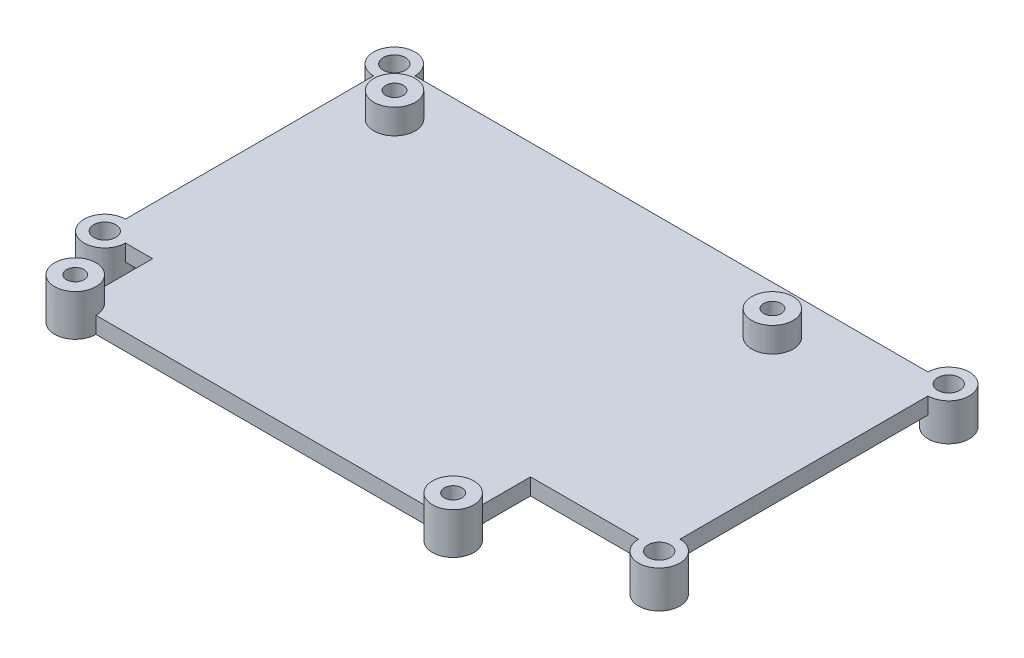
SolidWorks part; units mm, degrees
ref_plane "Front Plane" through (0, 0, 0) normal (0, 0, 1) x (1, 0, 0)
ref_plane "Top Plane" through (0, 0, 0) normal (0, 1, 0) x (1, 0, 0)
ref_plane "Right Plane" through (0, 0, 0) normal (1, 0, 0) x (0, 0, -1)
sketch "Sketch3" plane through (0, 0, 0) normal (0, 1, 0) x (1, 0, 0)
  line L0 (100.3619, -106.6601) -> (100.3619, -115.3602)
  line L9 (96.1939, -62.2252) -> (174.9339, -62.2252)
  line L10 (93.0189, -65.4002) -> (93.0189, -103.4892)
  line L11 (96.196, -106.664) -> (96.196, -106.6642)
  line L12 (96.196, -106.6601) -> (100.3619, -106.6601)
  line L13 (178.111, -65.3961) -> (178.111, -103.4851)
  line L16 (103.5369, -118.5352) -> (155.1869, -118.5352)
  line L18 (158.3619, -106.6601) -> (174.936, -106.6601)
  line L19 (158.3619, -106.6601) -> (158.3619, -115.3602)
  arc A8 (96.1939, -62.2252) -> (93.0189, -65.4002) centre (93.0189, -62.2252) ccw
  arc A9 (93.0189, -103.4892) -> (96.196, -106.6601) centre (93.021, -106.6642) ccw
  arc A10 (174.936, -106.6601) -> (178.111, -103.4851) centre (178.111, -106.6601) ccw
  circle A14 centre (178.1089, -62.2211) radius 1.7 construction
  circle A15 centre (178.111, -106.6601) radius 1.7 construction
  circle A16 centre (93.021, -106.6642) radius 1.7 construction
  circle A17 centre (93.0189, -62.2252) radius 1.7 construction
  circle A18 centre (178.1089, -62.2211) radius 1.7
  circle A19 centre (178.111, -106.6601) radius 1.7
  circle A20 centre (93.021, -106.6642) radius 1.7
  circle A21 centre (93.0189, -62.2252) radius 1.7
  arc A23 (158.3619, -70.8852) -> (158.3619, -68.1852) centre (158.3619, -69.5352) ccw construction
  arc A24 (158.3619, -68.1852) -> (158.3619, -70.8852) centre (158.3619, -69.5352) ccw construction
  arc A25 (158.3619, -119.8852) -> (158.3619, -117.1852) centre (158.3619, -118.5352) ccw construction
  arc A26 (158.3619, -117.1852) -> (158.3619, -119.8852) centre (158.3619, -118.5352) ccw construction
  arc A27 (100.3619, -119.8852) -> (100.3619, -117.1852) centre (100.3619, -118.5352) ccw construction
  arc A28 (100.3619, -117.1852) -> (100.3619, -119.8852) centre (100.3619, -118.5352) ccw construction
  arc A29 (100.3619, -70.8852) -> (100.3619, -68.1852) centre (100.3619, -69.5352) ccw construction
  arc A30 (100.3619, -68.1852) -> (100.3619, -70.8852) centre (100.3619, -69.5352) ccw construction
  arc A31 (158.3619, -70.8852) -> (158.3619, -68.1852) centre (158.3619, -69.5352) ccw
  arc A32 (158.3619, -68.1852) -> (158.3619, -70.8852) centre (158.3619, -69.5352) ccw
  arc A33 (158.3619, -119.8852) -> (158.3619, -117.1852) centre (158.3619, -118.5352) ccw
  arc A34 (158.3619, -117.1852) -> (158.3619, -119.8852) centre (158.3619, -118.5352) ccw
  arc A35 (100.3619, -119.8852) -> (100.3619, -117.1852) centre (100.3619, -118.5352) ccw
  arc A36 (100.3619, -117.1852) -> (100.3619, -119.8852) centre (100.3619, -118.5352) ccw
  arc A37 (100.3619, -70.8852) -> (100.3619, -68.1852) centre (100.3619, -69.5352) ccw
  arc A38 (100.3619, -68.1852) -> (100.3619, -70.8852) centre (100.3619, -69.5352) ccw
  arc A39 (100.3619, -115.3602) -> (103.5369, -118.5352) centre (100.3619, -118.5352) ccw
  arc A40 (155.1869, -118.5352) -> (158.3619, -115.3602) centre (158.3619, -118.5352) ccw
  circle A41 centre (100.3619, -69.5352) radius 3.175
  circle A42 centre (158.3619, -69.5352) radius 3.175
  arc A43 (178.111, -65.3961) -> (174.9339, -62.2252) centre (178.1089, -62.2211) ccw
  arc A44 (93.0189, -65.4002) -> (96.1939, -62.2252) centre (93.0189, -62.2252) ccw
  arc A45 (93.0189, -103.4892) -> (96.196, -106.6601) centre (93.021, -106.6642) cw
  arc A46 (100.3619, -115.3602) -> (103.5369, -118.5352) centre (100.3619, -118.5352) cw
  arc A47 (155.1869, -118.5352) -> (158.3619, -115.3602) centre (158.3619, -118.5352) ccw
  arc A48 (155.1869, -118.5352) -> (158.3619, -115.3602) centre (158.3619, -118.5352) ccw
  arc A49 (174.9339, -62.2252) -> (178.111, -65.3961) centre (178.1089, -62.2211) ccw
  arc A50 (178.111, -103.4851) -> (174.936, -106.6601) centre (178.111, -106.6601) ccw
  arc A51 (158.3619, -115.3602) -> (155.1869, -118.5352) centre (158.3619, -118.5352) ccw
  point P0 (0, 0)
  dimension "D1" = 6.35
  dimension "D2" = 6.35
extrude "Boss-Extrude2" add sketch "Sketch3" along normal blind 2.54 contours A8 A9 A10 | A21 A8 | A21 A8 | A20 A9 | A20 A9 | A19 A10 | A19 A10 | A18 | A18 | A39 A36 A35 | A41 A38 A37 | A42 A32 A31 | A40 A34 A33 | A51 L19 L18 A50 L13 A49 L9 A44 L10 A45 L12 L0 A46 L16 A41 A42 region at (134.6975, 0, 88.989) region at (102.5435, 0, 116.3536) region at (96.1062, 0, 106.6621) region at (156.1803, 0, 116.3536) region at (90.8373, 0, 60.0436) region at (180.2883, 0, 60.0374) region at (175.9294, 0, 104.4786) region at (97.2767, 0, 69.5352) region at (155.2767, 0, 69.5352)
extrude "Boss-Extrude3" add sketch "Sketch3<3>" against normal blind 3.175 contours A20 A9 | A20 A9 | A21 A8 | A21 A8 | A18 | A18 | A19 A10 | A19 A10 region at (96.1062, 0, 106.6621) region at (90.8373, 0, 60.0436) region at (180.2883, 0, 60.0374) region at (175.9294, 0, 104.4786)
sketch "Sketch3<3>" plane through (0, 0, 0) normal (0, 1, 0) x (1, 0, 0) same geometry as "Sketch3"
extrude "Boss-Extrude4" add sketch "Sketch3<4>" along normal blind 6.35 contours A46 A39 A36 A35 | A41 A38 A37 | A42 A32 A31 | A40 A51 A34 A33 region at (102.5435, 0, 116.3536) region at (156.1803, 0, 116.3536) region at (97.2767, 0, 69.5352) region at (155.2767, 0, 69.5352)
sketch "Sketch3<4>" plane through (0, 0, 0) normal (0, 1, 0) x (1, 0, 0) same geometry as "Sketch3"
